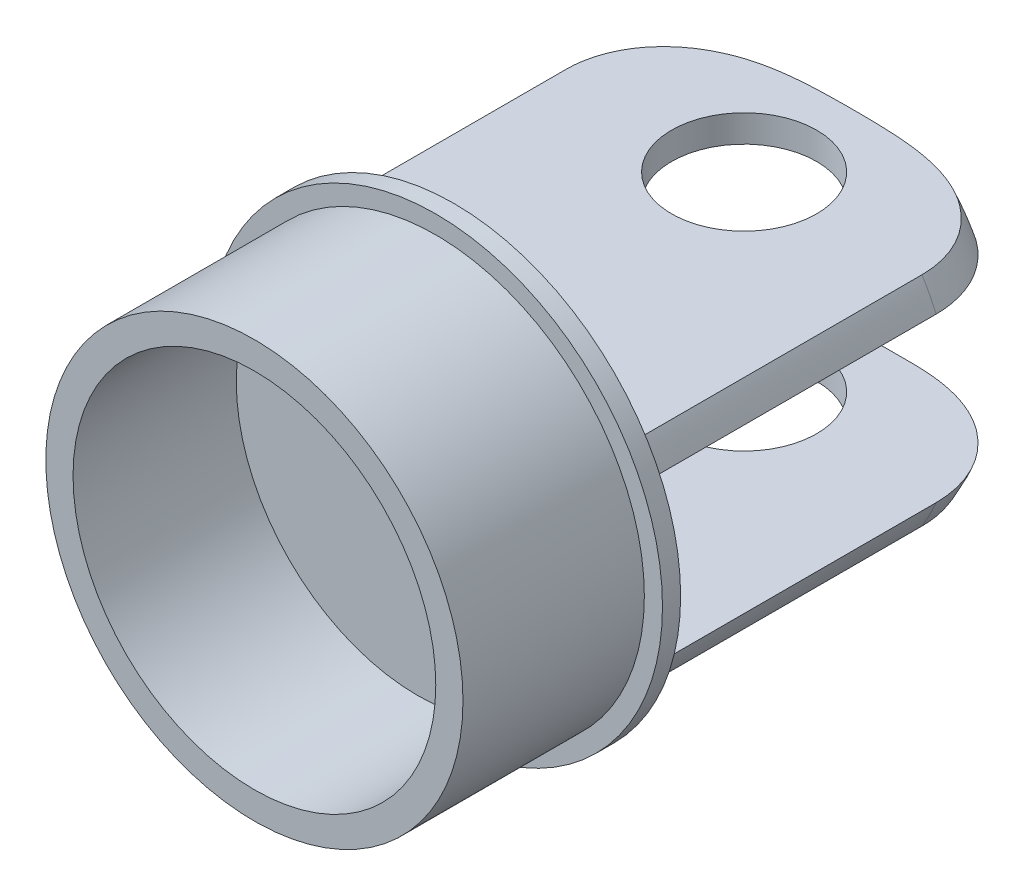
SolidWorks part; units mm, degrees
ref_plane "Front Plane" through (0, 0, 0) normal (0, 0, 1) x (1, 0, 0)
ref_plane "Top Plane" through (0, 0, 0) normal (0, 1, 0) x (1, 0, 0)
ref_plane "Right Plane" through (0, 0, 0) normal (1, 0, 0) x (0, 0, -1)
sketch "Sketch1" plane through (0, 0, 0) normal (0, 0, 1) x (1, 0, 0)
  line L0 (-9.8107, 6) -> (9.8107, 6)
  line L1 (-10.583, -4.5) -> (10.583, -4.5)
  line L2 (-11, -3.3541) -> (-11, 3.3541)
  line L3 (-10.583, 4.5) -> (10.583, 4.5)
  line L4 (11, -3.3541) -> (11, 3.3541)
  line L7 (-9.8107, -6) -> (9.8107, -6)
  circle A0 centre (0, 0) radius 12.5
  circle A1 centre (0, 0) radius 11.5
  dimension "D1" = 25
  dimension "D2" = 1
  dimension "D3" = 22
  dimension "D4" = 9
  dimension "D5" = 1.5
  dimension "D6" = 1.5
extrude "Boss-Extrude1" add sketch "Sketch1" along normal blind 10 contours L0 A1 | L3 A1 L0 | L4 A1 L3 L2 L1 | L4 A1 | L7 A1 | L1 A1 L7 | L2 A1 region at (0, 8.2524, 0) region at (0, 5.2406, 0) region at (0, 0, 0) region at (-11.2004, 0, 0) region at (11.2004, 0, 0) region at (0, -5.2406, 0) region at (0, -8.2524, 0)
extrude "Boss-Extrude2" add sketch "Sketch1<3>" against normal blind 1 contours A0 A1 L3 L4 L1 L2 | L7 A1 | L1 A1 L7 | L4 A1 L3 L2 L1 | L4 A1 | L3 A1 L0 | L0 A1 | A1 L4 L3 | A1 L3 L2 | L2 A1 | A1 L2 L1 | A1 L1 L4 | L4 L3 L2 L1 region at (0, 8.2524, 0) region at (0, 5.2406, 0) region at (0, 0, 0) region at (-11.2004, 0, 0) region at (11.2004, 0, 0) region at (0, -5.2406, 0) region at (0, -8.2524, 0) region at (-12.1464, 0, 0)
sketch "Sketch1<3>" plane through (0, 0, 0) normal (0, 0, 1) x (1, 0, 0) same geometry as "Sketch1"
extrude "Boss-Extrude3" add sketch "Sketch1<5>" against normal blind 22 from offset 1 separate body contours L3 A1 L0 | L1 A1 L7 region at (0, 5.2406, 0) region at (0, -5.2406, 0) offset against normal yes
sketch "Sketch1<5>" plane through (0, 0, 0) normal (0, 0, 1) x (1, 0, 0) same geometry as "Sketch1"
sketch "Sketch2" plane through (0, -6, 0) normal (0, -1, 0) x (1, 0, 0)
  line L0 (-12.5, -1) -> (12.5, -1) construction
  circle A0 centre (0, -17) radius 4
  point P2 (0, 0)
  dimension "D1" = 8
  dimension "D2" = 16
extrude "Cut-Extrude1" cut sketch "Sketch2" against normal through all
fillet "Fillet1" radius 6 2 edges at (-10.2244, -5.2642, -23) (10.2244, -5.2642, -23)
fillet "Fillet4" radius 6 1 edges at (-10.2244, 5.2642, -23)
sketch "Sketch3" plane through (0, 0, 10) normal (0, 0, 1) x (1, 0, 0)
  circle A0 centre (0, 0) radius 10
  circle A1 centre (0, 0) radius 11.5
  circle A2 centre (0, 0) radius 11.5
  dimension "D1" = 0
  dimension "D2" = 1.5
extrude "Cut-Extrude2" cut sketch "Sketch3" against normal blind 9 contours A0 region at (0, 0, 10)
